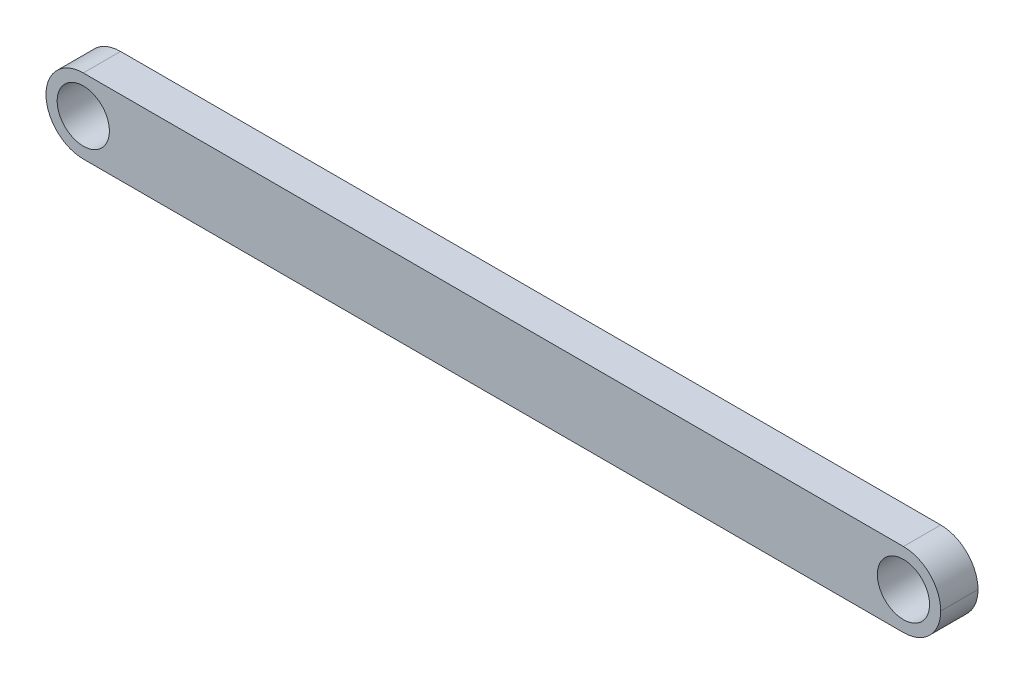
SolidWorks part; units mm, degrees
ref_plane "前视基准面" through (0, 0, 0) normal (0, 0, 1) x (1, 0, 0)
ref_plane "上视基准面" through (0, 0, 0) normal (0, 1, 0) x (1, 0, 0)
ref_plane "右视基准面" through (0, 0, 0) normal (1, 0, 0) x (0, 0, -1)
other "Configuration Table"
sketch "草图1" plane through (0, 0, 0) normal (0, 0, 1) x (1, 0, 0)
  line L1 (-120, -10) -> (120, -10)
  line L2 (-120, -10) -> (-120, 10)
  line L3 (-120, 10) -> (120, 10)
  line L4 (120, -10) -> (120, 10)
  line L5 (-120, -10) -> (120, 10) construction
  line L6 (-120, 10) -> (120, -10) construction
  circle A0 centre (-110, 0) radius 7
  circle A1 centre (110, 0) radius 7
  point P0 (0, 0)
  dimension "D3" = 14
  dimension "D4" = 14
  dimension "D1" = 20
  dimension "D2" = 240
  dimension "D5" = 110
  dimension "D6" = 110
extrude "凸台-拉伸1" add sketch "草图1" along normal blind 10
fillet "圆角1" radius 10 4 edges at (120, 10, 5) (120, -10, 5) (-120, -10, 5) (-120, 10, 5)
